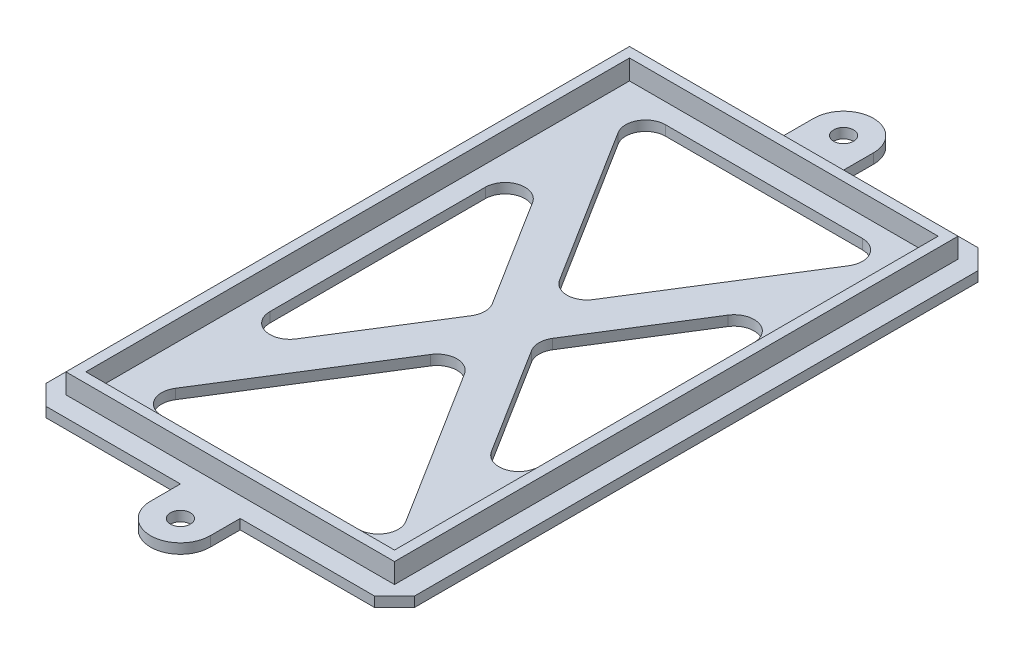
SolidWorks part; units mm, degrees
ref_plane "Front Plane" through (0, 0, 0) normal (0, 0, 1) x (1, 0, 0)
ref_plane "Top Plane" through (0, 0, 0) normal (0, 1, 0) x (1, 0, 0)
ref_plane "Right Plane" through (0, 0, 0) normal (1, 0, 0) x (0, 0, -1)
sketch "Sketch1" plane through (0, 0, 0) normal (0, 1, 0) x (1, 0, 0)
  line L8 (1.27, 1.27) -> (1.27, -70.612)
  line L9 (0, 0) -> (-39.37, 0)
  line L10 (0, 0) -> (0, -69.342)
  line L11 (0, -69.342) -> (-39.37, -69.342)
  line L12 (-39.37, 0) -> (-39.37, -69.342)
  line L13 (1.27, -70.612) -> (-40.64, -70.612)
  line L14 (-40.64, 1.27) -> (-40.64, -70.612)
  line L15 (1.27, 1.27) -> (-40.64, 1.27)
  dimension "D1" = 39.37
  dimension "D2" = 69.342
  dimension "D3" = 1.27
extrude "Boss-Extrude4" add sketch "Sketch1" along normal blind 2.54
sketch "Sketch5" plane through (0, 0, 0) normal (0, -1, 0) x (1, 0, 0)
  line L14 (-43.18, -3.81) -> (3.81, -3.81)
  line L15 (3.81, -3.81) -> (3.81, 73.152)
  line L16 (-43.18, 73.152) -> (-43.18, -3.81)
  line L17 (3.81, 73.152) -> (-43.18, 73.152)
  line L18 (-43.18, -3.81) -> (3.81, -3.81)
  line L19 (3.81, -3.81) -> (3.81, 73.152)
  line L20 (-43.18, 73.152) -> (-43.18, -3.81)
  line L21 (3.81, 73.152) -> (-43.18, 73.152)
  dimension "D1" = 2.54
extrude "Boss-Extrude5" add sketch "Sketch5" along normal blind 1.27
chamfer "Chamfer4" distance 2.54 angle 45 4 edges at (-43.18, -0.635, 73.152) (3.81, -0.635, 73.152) (3.81, -0.635, -3.81) (-43.18, -0.635, -3.81)
sketch "Sketch6" plane through (0, 0, 0) normal (0, 1, 0) x (1, 0, 0)
  line L0 (0, 0) -> (-39.37, 0) construction
  line L1 (-36.83, -2.54) -> (-2.54, -2.54)
  line L2 (-36.83, -12.1041) -> (-36.83, -57.2379)
  line L3 (-36.83, -66.802) -> (-2.54, -66.802)
  line L4 (-2.54, -12.1041) -> (-2.54, -57.2379)
  line L5 (0, -69.342) -> (0, 0) construction
  line L6 (-39.37, -69.342) -> (0, -69.342) construction
  line L7 (-39.37, 0) -> (-39.37, -69.342) construction
  line L8 (-36.83, -57.2379) -> (-22.6828, -34.671)
  line L9 (-2.54, -12.1041) -> (-16.6872, -34.671)
  line L10 (-36.83, -12.1041) -> (-22.6828, -34.671)
  line L11 (-36.83, -2.54) -> (-19.685, -29.889)
  line L12 (-19.685, -39.453) -> (-2.54, -66.802)
  line L13 (-16.6872, -34.671) -> (-2.54, -57.2379)
  line L14 (-19.685, -29.889) -> (-2.54, -2.54)
  line L15 (-19.685, -39.453) -> (-36.83, -66.802)
  line L16 (-40.64, -70.612) -> (1.27, -70.612) construction
  point P3 (-19.685, -70.612)
  point P24 (0, -34.671)
  dimension "D1" = 2.54
  dimension "D2" = 2.54
  dimension "D3" = 2.54
  dimension "D4" = 2.54
  dimension "D5" = 5.08
  dimension "D6" = 5.08
  dimension "D7" = 2.54
extrude "Cut-Extrude1" cut sketch "Sketch6" against normal blind 2.54
fillet "Fillet1" radius 2.54 12 edges at (-19.685, -0.635, 39.453) (-36.83, -0.635, 66.802) (-2.54, -0.635, 57.2379) (-2.54, -0.635, 12.1041) (-16.6872, -0.635, 34.671) (-22.6828, -0.635, 34.671) (-19.685, -0.635, 29.889) (-2.54, -0.635, 2.54) (-36.83, -0.635, 12.1041) (-2.54, -0.635, 66.802) (-36.83, -0.635, 57.2379) (-36.83, -0.635, 2.54)
sketch "Sketch7" plane through (0, 0, 0) normal (0, 1, 0) x (1, 0, 0)
  line L0 (-40.64, 3.81) -> (1.27, 3.81) construction
  line L1 (-15.875, 7.62) -> (-15.875, 3.81)
  line L2 (-15.875, 3.81) -> (-23.495, 3.81)
  line L3 (-23.495, 3.81) -> (-23.495, 7.62)
  line L4 (-996.19, -34.671) -> (49003.81, -34.671)
  line L5 (3.81, 1.27) -> (3.81, -70.612) construction
  line L6 (-23.495, -73.152) -> (-23.495, -76.962)
  line L7 (-15.875, -73.152) -> (-23.495, -73.152)
  line L8 (-15.875, -76.962) -> (-15.875, -73.152)
  circle A0 centre (-19.685, 7.62) radius 1.27
  arc A1 (-15.875, 7.62) -> (-23.495, 7.62) centre (-19.685, 7.62) ccw
  arc A2 (-15.875, -76.962) -> (-23.495, -76.962) centre (-19.685, -76.962) cw
  circle A3 centre (-19.685, -76.962) radius 1.27
  point P6 (-19.685, 3.81)
  point P14 (3.81, -34.671)
  dimension "D1" = 2.54
  dimension "D2" = 2.54
  dimension "D3" = 3.81
extrude "Boss-Extrude6" add sketch "Sketch7" against normal blind 1.27
